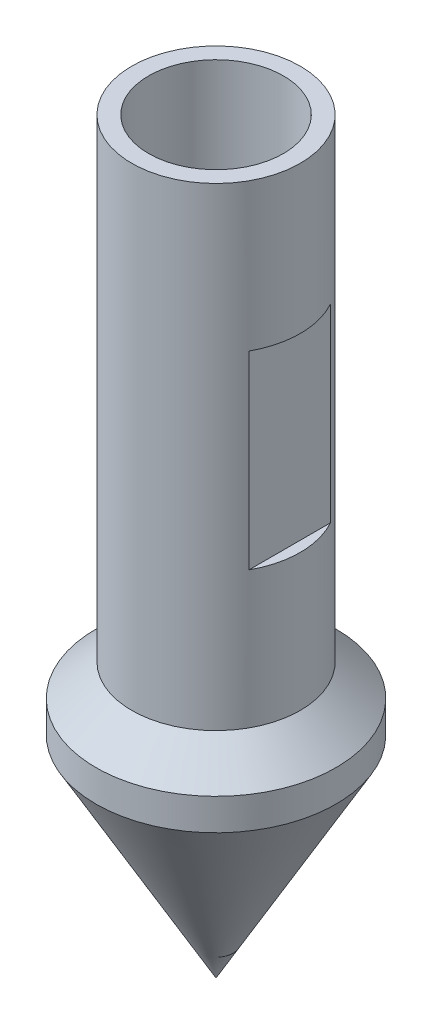
SolidWorks part; units mm, degrees
ref_plane "Front Plane" through (0, 0, 0) normal (0, 0, 1) x (1, 0, 0)
ref_plane "Top Plane" through (0, 0, 0) normal (0, 1, 0) x (1, 0, 0)
ref_plane "Right Plane" through (0, 0, 0) normal (1, 0, 0) x (0, 0, -1)
sketch "Sketch1" plane through (0, 0, 0) normal (0, 0, 1) x (1, 0, 0)
  line L0 (0, -7.6071) -> (0, 15.5)
  line L1 (0, 15.5) -> (-4, 15.5)
  line L2 (-4, 15.5) -> (-4, -7)
  line L3 (-4, -7) -> (-5.7, -8.5)
  line L4 (-5.7, -8.5) -> (-5.7, -10)
  line L5 (-5.7, -10) -> (0, -20)
  line L6 (0, -20) -> (0, -7.6071)
  dimension "D1" = 35.5
  dimension "D2" = 4
  dimension "D3" = 22.5
  dimension "D4" = 10
  dimension "D5" = 1.5
  dimension "D6" = 5.7
  dimension "D7" = 20
revolve "Revolve1" add sketch "Sketch1" angle 360 about L0
sketch "Sketch2" plane through (0, 15.5, 0) normal (0, 1, 0) x (1, 0, 0)
  circle A0 centre (0, 0) radius 3.2
  dimension "D1" = 6.4
extrude "Cut-Extrude1" cut sketch "Sketch2" against normal blind 9.5
sketch "Sketch3" plane through (0, 0, 0) normal (0, 0, 1) x (1, 0, 0)
  line L0 (4, 15.5) -> (-4, 15.5) construction
  line L1 (-7.5, 8.5) -> (-3.5, 8.5)
  line L2 (-7.5, 8.5) -> (-7.5, -0.5)
  line L3 (-7.5, -0.5) -> (-3.5, -0.5)
  line L4 (-3.5, 8.5) -> (-3.5, -0.5)
  line L5 (7.5, 8.5) -> (3.5, 8.5)
  line L6 (7.5, 8.5) -> (7.5, -0.5)
  line L7 (7.5, -0.5) -> (3.5, -0.5)
  line L8 (3.5, 8.5) -> (3.5, -0.5)
  line L9 (3.2, 15.5) -> (-3.2, 15.5) construction
  dimension "D1" = 9
  dimension "D2" = 9
  dimension "D3" = 7
  dimension "D4" = 7
  dimension "D5" = 7
  dimension "D6" = 3.5
  dimension "D7" = 4
  dimension "D8" = 4
extrude "Cut-Extrude2" cut sketch "Sketch3" against normal blind 9.5 and the other way blind 9.5
